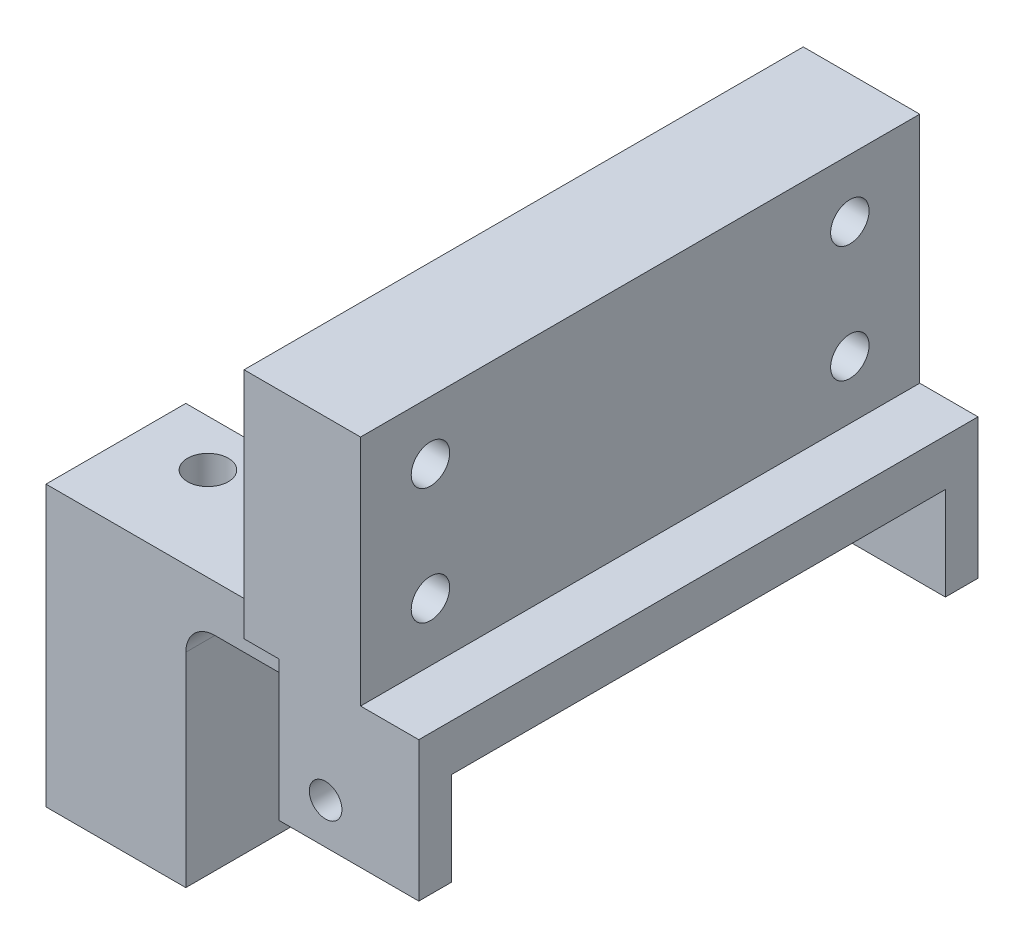
SolidWorks part; units mm, degrees
material "ABS"
ref_plane "前视基准面" through (0, 0, 0) normal (0, 0, 1) x (1, 0, 0)
ref_plane "上视基准面" through (0, 0, 0) normal (0, 1, 0) x (1, 0, 0)
ref_plane "右视基准面" through (0, 0, 0) normal (1, 0, 0) x (0, 0, -1)
sketch "草图1" plane through (0, 0, 0) normal (0, 1, 0) x (1, 0, 0)
  line L1 (-10, -24) -> (10, -24)
  line L2 (-10, -24) -> (-10, 24)
  line L3 (-10, 24) -> (10, 24)
  line L4 (10, -24) -> (10, 24)
  line L5 (-10, -24) -> (10, 24) construction
  line L6 (-10, 24) -> (10, -24) construction
  point P0 (0, 0)
  dimension "D1" = 20
  dimension "D2" = 48
extrude "凸台-拉伸2" add sketch "草图1" along normal blind 4
sketch "草图3" plane through (0, 0, 0) normal (0, -1, 0) x (1, 0, 0)
  line L0 (10, 24) -> (10, -24) construction
  line L1 (-10, 24) -> (10, 24)
  line L2 (-10, 24) -> (-10, 21)
  line L3 (-10, 21) -> (10, 21)
  line L4 (10, 24) -> (10, 21)
  line L5 (-10, 0) -> (10, 0) construction
  line L6 (-10, -24) -> (-10, 24) construction
  line L7 (-10, -21) -> (10, -21)
  line L8 (10, -24) -> (10, -21)
  line L9 (-10, -24) -> (10, -24)
  line L10 (-10, -24) -> (-10, -21)
  dimension "D1" = 3
extrude "凸台-拉伸3" add sketch "草图3" along normal blind 8
sketch "草图4" plane through (-10, 0, 0) normal (-1, 0, 0) x (0, 0, 1)
  line L0 (-24, 4) -> (24, 4) construction
  line L1 (-21, 0) -> (-9, 0)
  line L2 (-21, 0) -> (-21, 4)
  line L3 (-21, 4) -> (-9, 4)
  line L4 (-9, 0) -> (-9, 4)
  dimension "D1" = 12
extrude "凸台-拉伸4" add sketch "草图4" along normal blind 15
sketch "草图5" plane through (0, 4, 0) normal (0, 1, 0) x (1, 0, 0)
  line L0 (-10, 9) -> (-10, -24) construction
  line L1 (10, 24) -> (-10, 24) construction
  circle A0 centre (-19.1, 13) radius 1.75
  dimension "D1" = 3.5
  dimension "D2" = 9.1
  dimension "D3" = 11
extrude "切除-拉伸2" cut sketch "草图5" against normal through all
sketch "草图6" plane through (0, 0, 0) normal (0, -1, 0) x (1, 0, 0)
  line L0 (-25, -9) -> (-10, -9) construction
  line L1 (-25, -21) -> (-13, -21)
  line L2 (-25, -21) -> (-25, -9)
  line L3 (-25, -9) -> (-13, -9)
  line L4 (-13, -21) -> (-13, -9)
  circle A0 centre (-19.1, -13) radius 1.75 construction
  circle A1 centre (-19.1, -13) radius 1.75
  dimension "D1" = 12
extrude "凸台-拉伸5" add sketch "草图6" along normal blind 20
sketch "草图7" plane through (0, 4, 0) normal (0, 1, 0) x (1, 0, 0)
  line L0 (10, 24) -> (-10, 24) construction
  line L1 (-5, -24) -> (5, -24)
  line L2 (-5, -24) -> (-5, 24)
  line L3 (-5, 24) -> (5, 24)
  line L4 (5, -24) -> (5, 24)
  line L5 (-5, -24) -> (5, 24) construction
  line L6 (-5, 24) -> (5, -24) construction
  point P0 (0, 0)
  dimension "D1" = 10
extrude "凸台-拉伸6" add sketch "草图7" along normal blind 20
sketch "草图8" plane through (5, 0, 0) normal (1, 0, 0) x (0, 0, -1)
  line L0 (0, 4) -> (0, 24) construction
  line L1 (-24, 4) -> (24, 4) construction
  line L2 (-24, 24) -> (24, 24) construction
  line L3 (-24, 14) -> (24, 14) construction
  line L4 (-24, 24) -> (-24, 4) construction
  line L5 (24, 24) -> (24, 4) construction
  line L7 (-18, 9) -> (18, 9) construction
  line L8 (-18, 9) -> (-18, 19) construction
  line L9 (-18, 19) -> (18, 19) construction
  line L10 (18, 9) -> (18, 19) construction
  line L11 (-18, 9) -> (18, 19) construction
  line L12 (-18, 19) -> (18, 9) construction
  circle A2 centre (-18, 19) radius 1.65
  circle A3 centre (18, 19) radius 1.65
  circle A4 centre (18, 9) radius 1.65
  circle A5 centre (-18, 9) radius 1.65
  point P12 (0, 14)
  dimension "D1" = 36
  dimension "D3" = 3.3
  dimension "D2" = 10
extrude "切除-拉伸3" cut sketch "草图8" against normal through all
chamfer "倒角1" distance 3 angle 45 1 edges at (-10, -2, -24)
fillet "圆角2" radius 2.5 1 edges at (-13, 0, -15)
sketch "草图11" plane through (0, 0, -24) normal (0, 0, -1) x (-1, 0, 0)
  line L0 (7, -8) -> (-10, -8) construction
  line L1 (10, 4) -> (2, 4)
  line L2 (10, 4) -> (10, -8)
  line L3 (10, -8) -> (2, -8)
  line L4 (2, 4) -> (2, -8)
  dimension "D1" = 8
extrude "切除-拉伸5" cut sketch "草图11" against normal blind 3
sketch "草图12" plane through (0, 0, 24) normal (0, 0, 1) x (1, 0, 0)
  line L2 (-10, 0) -> (10, 0) construction
  line L3 (10, 4) -> (10, -8) construction
  circle A0 centre (2, -4.5) radius 1.4
  dimension "D2" = 2.8
  dimension "D1" = 4.5
  dimension "D3" = 8
extrude "切除-拉伸6" cut sketch "草图12" against normal through all
chamfer "倒角2" distance 1.5 angle 45 1 edges at (3.4, -4.5, 24)
sketch "草图14" plane through (0, -8, 0) normal (0, -1, 0) x (1, 0, 0)
  line L0 (-10, 24) -> (-10, 21) construction
  line L1 (-10, 21.2) -> (11.2744, 21.2)
  line L2 (-10, 21.2) -> (-10, -21.2)
  line L3 (-10, -21.2) -> (11.2744, -21.2)
  line L4 (11.2744, 21.2) -> (11.2744, -21.2)
  line L5 (-10, 21) -> (10, 21) construction
  line L6 (10, -21) -> (-2, -21) construction
  dimension "D1" = 0.2
  dimension "D2" = 0.2
extrude "切除-拉伸7" cut sketch "草图14" against normal blind 8
ref_plane "基准面1" through (0, 0, -34) normal (0, 0, -1) x (-1, 0, 0)
mirror "镜向2" about plane through (0, 0, -34) normal (0, 0, -1) of bodies 119
sketch "草图15" plane through (0, 24, 0) normal (0, 1, 0) x (1, 0, 0)
  line L1 (-70.7163, 36.3704) -> (32.9261, 36.3704)
  line L2 (-70.7163, 36.3704) -> (-70.7163, -30.4904)
  line L3 (-70.7163, -30.4904) -> (32.9261, -30.4904)
  line L4 (32.9261, 36.3704) -> (32.9261, -30.4904)
extrude "切除-拉伸8" cut sketch "草图15" against normal through all
